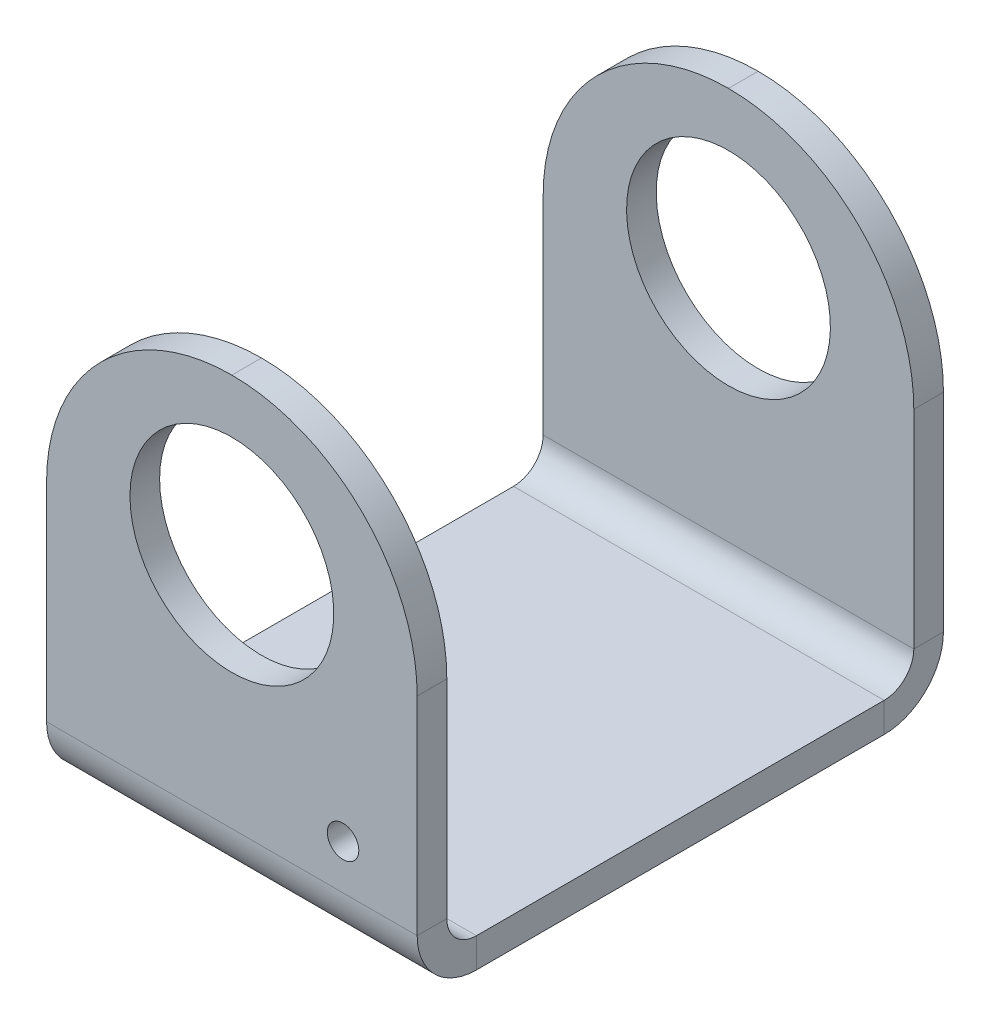
SolidWorks part; units mm, degrees
note: The reader was unsure of these and kept them because the rebuilt part matched: flange length of "边线-法兰3".
material "Q355"
ref_plane "前视基准面" through (0, 0, 0) normal (0, 0, 1) x (1, 0, 0)
ref_plane "上视基准面" through (0, 0, 0) normal (0, 1, 0) x (1, 0, 0)
ref_plane "右视基准面" through (0, 0, 0) normal (1, 0, 0) x (0, 0, -1)
sketch "草图10" plane through (0, 0, 0) normal (0, 1, 0) x (1, 0, 0)
  line L0 (50, 55) -> (-50, -55) construction
  line L1 (-50, 55) -> (50, 55)
  line L2 (-50, 55) -> (-50, -55)
  line L3 (-50, -55) -> (50, -55)
  line L4 (50, 55) -> (50, -55)
  dimension "D1" = 100
  dimension "D2" = 110
base flange "基体-法兰2" sketch "草图10" thickness 8 reverse thickness direction no parameters "D1"=8
edge flange "边线-法兰3" sketch "草图17" flange profiles "草图17", "草图18" flange angle 90 flange length 122 flange position bend outside bend radius 8 thickness 8 relief rectangular parameters "D6"=10, "D8"=1
sketch "草图17" plane through (0, 0, 55) normal (0, 0, 1) x (1, 0, 0)
  line L0 (-50, 0) -> (50, 0) construction
  line L1 (-50, 0) -> (50, 0)
  line L2 (-50, 0) -> (-50, 114)
  line L4 (50, 114) -> (50, 0)
  line L5 (50, -8) -> (-50, -8) construction
  line L6 (-50, 114) -> (50, 114)
  circle A1 centre (0, 72) radius 27.5
  dimension "D1" = 80
  dimension "D2" = 55
  dimension "D3" = 42
  dimension "D4" = 50
sketch "草图18" plane through (0, 0, -55) normal (0, 0, -1) x (-1, 0, 0)
  line L0 (-50, 0) -> (50, 0) construction
  line L1 (-50, 0) -> (50, 0)
  line L2 (-50, 0) -> (-50, 114)
  line L4 (50, 114) -> (50, 0)
  line L5 (-50, -8) -> (50, -8) construction
  line L6 (-50, 114) -> (50, 114)
  circle A1 centre (0, 72) radius 27.5
  dimension "D1" = 80
  dimension "D2" = 55
  dimension "D3" = 42
  dimension "D4" = 50
bend "边线折弯3" bend radius 8 bend angle 90 parameters "D5"=1
bend "边线折弯4" bend radius 8 bend angle 90 parameters "D5"=2
hole_wizard "M10 螺纹孔1" positions "草图19" profile "草图20" tap size "M10" standard "GB"
sketch "草图19" plane through (0, 0, 71) normal (0, 0, 1) x (1, 0, 0)
  line L0 (30, 20.0385) -> (0, 72) construction
  line L2 (50, 8) -> (50, 114) construction
  circle A0 centre (0, 72) radius 27.5 construction
  point P0 (30, 20.0385)
  dimension "D1" = 60
  dimension "D2" = 30
sketch "草图20" plane through (30, 20.0385, 71) normal (1, 0, 0) x (0, -1, 0)
  line L0 (0, 0) -> (0, 30.0537)
  line L1 (0, 30.0537) -> (4.25, 27.5)
  line L2 (4.25, 27.5) -> (4.25, 0)
  line L5 (4.25, 0) -> (0, 0)
  line L10 (0, 30.0537) -> (-4.25, 27.5) construction
  line L11 (0, -6.35) -> (0, 107.95) construction
  dimension "螺纹孔钻头直径" = 8.5
  dimension "螺纹孔钻头深度" = 27.5
  dimension "导头角度" = 118
cosmetic thread "孔螺蚊线1"
fillet "圆角1" radius 50 4 edges at (50, 114, -67) (-50, 114, -67) (-50, 114, 67) (50, 114, 67)
sketch "折弯-线1" [suppressed] plane through (0, 0, 0) normal (0, 1, 0) x (1, 0, 0)
sketch "边界框1" [suppressed] plane through (0, 0, 0) normal (0, 1, 0) x (1, 0, 0)
sheet metal parameters "钣金11" thickness 8 parameters "D1"=10
flat pattern "平板型式11" [suppressed]
sketch "折弯-线3" plane through (0, 0, 0) normal (0, 1, 0) x (1, 0, 0)
sketch "边界框3" [suppressed] plane through (0, 0, 0) normal (0, 1, 0) x (1, 0, 0)
sheet metal parameters "钣金12" thickness 8 parameters "D1"=10
flat pattern "平板型式11" [suppressed]
sketch "折弯-线3" plane through (0, 0, 0) normal (0, 1, 0) x (1, 0, 0)
sketch "边界框3" [suppressed] plane through (0, 0, 0) normal (0, 1, 0) x (1, 0, 0)
bend of the flat pattern "展开-<边线折弯3>1"
bend of the flat pattern "展开-<边线折弯4>1"
sheet metal parameters "钣金13" thickness 8 parameters "D1"=10
flat pattern "平板型式11"
sketch "折弯-线3" plane through (0, 0, 0) normal (0, 1, 0) x (1, 0, 0)
  line L0 (50, 64.4248) -> (-50, 64.4248) construction
  line L1 (-50, -64.4248) -> (50, -64.4248) construction
  line L2 (50, 64.4248) -> (-50, 64.4248) construction
  line L3 (-50, -64.4248) -> (50, -64.4248) construction
sketch3d "边界框3" [suppressed]
  line L0 (-50, 179.8495, 0) -> (-50, -179.8495, 0) construction
  line L1 (50, 179.8495, 0) -> (50, -179.8495, 0) construction
  line L2 (-50, 179.8495, 0) -> (50, 179.8495, 0) construction
  line L3 (-50, -179.8495, 0) -> (50, -179.8495, 0) construction
bend of the flat pattern "展开-<边线折弯3>1"
bend of the flat pattern "展开-<边线折弯4>1"
